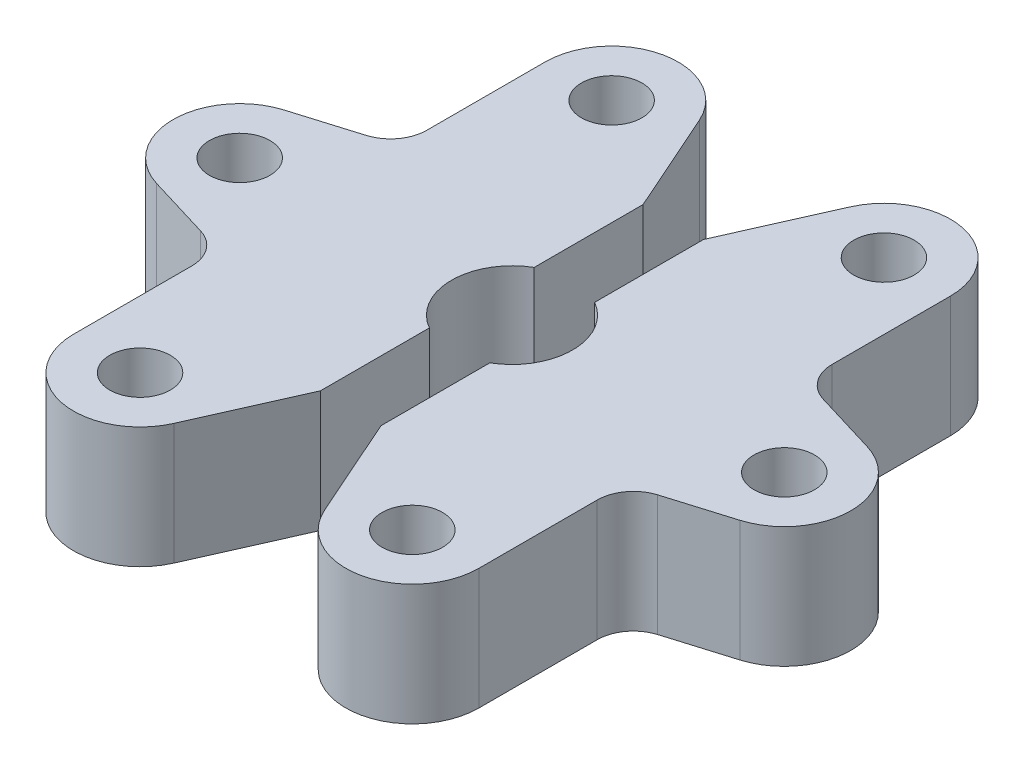
SolidWorks part; units mm, degrees
material "1060 Alloy"
ref_plane "Front Plane" through (0, 0, 0) normal (0, 0, 1) x (1, 0, 0)
ref_plane "Top Plane" through (0, 0, 0) normal (0, 1, 0) x (1, 0, 0)
ref_plane "Right Plane" through (0, 0, 0) normal (1, 0, 0) x (0, 0, -1)
ref_axis "Axis1" through (-88.99, 0, 0) along (1, 0, 0)
ref_axis "Axis2" through (0, 55, 0) along (0, -1, 0)
sketch "Sketch1" plane through (0, 0, 0) normal (0, 1, 0) x (1, 0, 0)
  line L0 (-88.99, 0) -> (88.99, 0) construction
  line L1 (0, 0) -> (0, 11.874) construction
  line L2 (0, 0) -> (-4.9056, 8.4967) construction
  line L3 (-16.75, 19.4856) -> (-16.75, -19.4856)
  line L4 (16.75, 19.4856) -> (16.75, -19.4856)
  line L5 (-2.5, 13.3301) -> (2.5, 13.3301) construction
  line L6 (-2.5, 13.3301) -> (-2.5, 4.3301)
  line L7 (2.5, 13.3301) -> (2.5, 4.3301)
  line L8 (-2.5, 13.3301) -> (-6.223, 21.7171)
  line L9 (2.5, 13.3301) -> (6.223, 21.7171)
  line L10 (-24.0925, 5.2644) -> (-16.75, 7.4856)
  line L11 (-24.0925, -5.2644) -> (-16.75, -7.4856)
  line L12 (-16.75, 7.4856) -> (-16.75, -7.4856) construction
  line L13 (24.0925, -5.2644) -> (16.75, -7.4856)
  line L14 (24.0925, 5.2644) -> (16.75, 7.4856)
  line L15 (-8.8618, 0) -> (10.083, 0) construction
  line L16 (2.5, -13.3301) -> (6.223, -21.7171)
  line L17 (2.5, -13.3301) -> (2.5, -4.3301)
  line L18 (-2.5, -13.3301) -> (-2.5, -4.3301)
  line L19 (-2.5, -13.3301) -> (-6.223, -21.7171)
  circle A0 centre (0, 0) radius 5
  circle A1 centre (0, 0) radius 22.5 construction
  circle A2 centre (-22.5, 0) radius 2.5
  circle A3 centre (-11.25, 19.4856) radius 2.5
  circle A4 centre (11.25, 19.4856) radius 2.5
  circle A5 centre (22.5, 0) radius 2.5
  circle A6 centre (11.25, -19.4856) radius 2.5
  circle A7 centre (-11.25, -19.4856) radius 2.5
  circle A8 centre (-22.5, 0) radius 5.5
  circle A9 centre (-11.25, 19.4856) radius 5.5
  circle A10 centre (11.25, 19.4856) radius 5.5
  circle A11 centre (22.5, 0) radius 5.5
  circle A12 centre (11.25, -19.4856) radius 5.5
  circle A13 centre (-11.25, -19.4856) radius 5.5
  point P21 (0, 0)
  point P36 (-16.75, 0)
  point P39 (0, 13.3301)
  point P41 (0, 5)
  dimension "D1" = 10
  dimension "D2" = 45
  dimension "D3" = 5
  dimension "D5" = 30
  dimension "D7" = 9
  dimension "D8" = 12
  dimension "D6" = 3
  dimension "D4" = 6
extrude "Boss-Extrude1" add sketch "Sketch1" along normal blind 10 contours A13 L19 L18 A0 L6 L8 A9 L3 | A12 L4 A10 L9 L7 A0 L17 L16 | A9 A3 | A8 A2 | A8 L11 L3 L10 | A13 A7 | A10 A4 | A11 A5 | A12 A6 | A11 L14 L4 L13 region at (-9.7197, 0, 0) region at (-12.3583, 0, -24.7138) region at (-16.9167, 0, 0) region at (-19.3147, 0, -4.2915) region at (-11.25, 0, 14.1411) region at (9.7197, 0, 0) region at (12.3583, 0, -24.7138) region at (10.1417, 0, 14.2573) region at (20.373, 0, -6.2154) region at (26.7915, 0, -3.1853)
fillet "Fillet1" radius 3 2 edges at (-16.75, 5, 7.4856) (-16.75, 5, -7.4856)
fillet "Fillet2" radius 3 2 edges at (16.75, 5, 7.4856) (16.75, 5, -7.4856)
sketch "草图1" plane through (0, 10, 0) normal (0, 1, 0) x (1, 0, 0)
  line B0 (16.75, 19.4856) -> (16.75, -19.4856)
  line B1 (-24.0925, -5.2644) -> (-16.75, -7.4856)
  line B2 (-24.0925, 5.2644) -> (-16.75, 7.4856)
  line B3 (2.5, 13.3301) -> (2.5, 4.3301)
  line B4 (2.5, 13.3301) -> (6.223, 21.7171)
  line B5 (-2.5, 13.3301) -> (-2.5, 4.3301)
  line B6 (-2.5, 13.3301) -> (-6.223, 21.7171)
  line B7 (-16.75, 19.4856) -> (-16.75, -19.4856)
  line B8 (-2.5, -13.3301) -> (-2.5, -4.3301)
  line B9 (-2.5, -13.3301) -> (-6.223, -21.7171)
  line B10 (2.5, -13.3301) -> (6.223, -21.7171)
  line B11 (2.5, -13.3301) -> (2.5, -4.3301)
  line B12 (24.0925, 5.2644) -> (16.75, 7.4856)
  line B13 (24.0925, -5.2644) -> (16.75, -7.4856)
  circle B14 centre (11.25, 19.4856) radius 2.5
  circle B15 centre (-11.25, 19.4856) radius 2.5
  circle B16 centre (-22.5, 0) radius 2.5
  circle B17 centre (0, 0) radius 5
  circle B18 centre (22.5, 0) radius 5.5
  circle B19 centre (11.25, 19.4856) radius 5.5
  circle B20 centre (-11.25, 19.4856) radius 5.5
  circle B21 centre (-22.5, 0) radius 5.5
  circle B22 centre (-11.25, -19.4856) radius 2.5
  circle B23 centre (11.25, -19.4856) radius 2.5
  circle B24 centre (22.5, 0) radius 2.5
  circle B25 centre (-11.25, -19.4856) radius 5.5
  circle B26 centre (11.25, -19.4856) radius 5.5
sketch_block_instance "块1-1"
sketch_block "块1"
